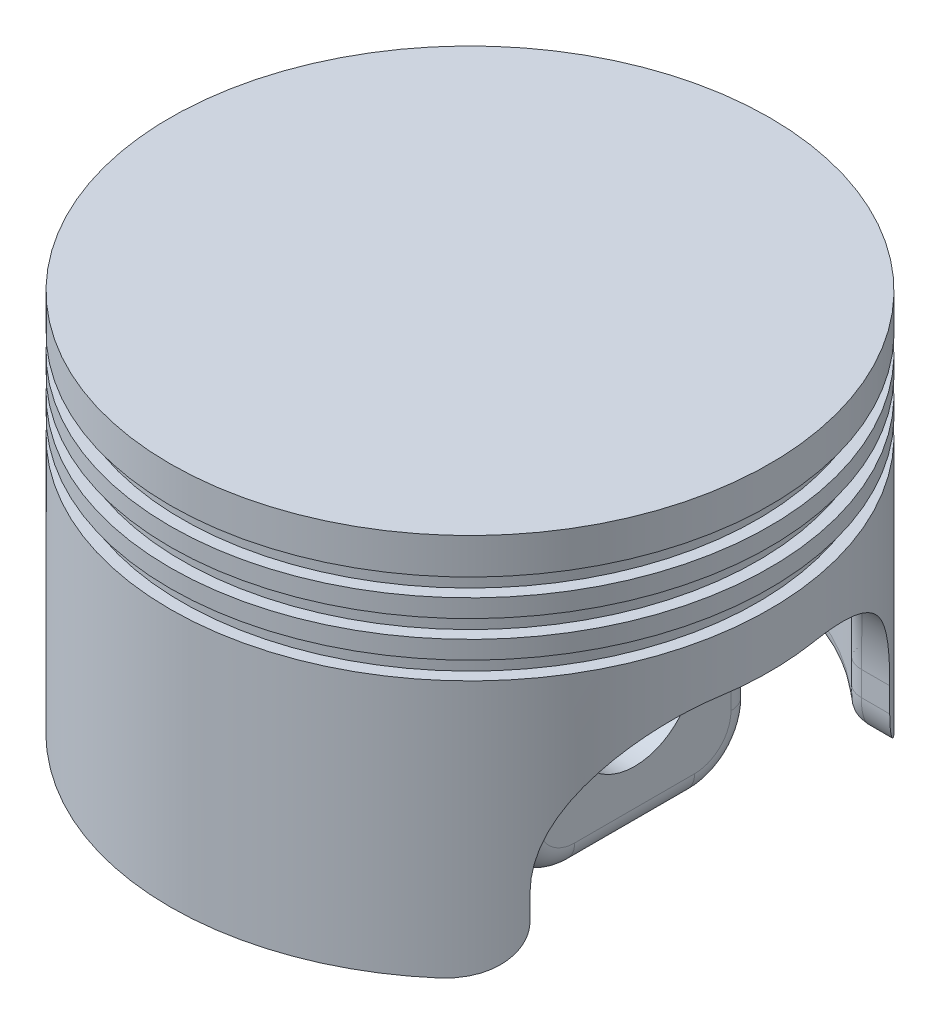
SolidWorks part; units mm, degrees
ref_plane "Alzado" through (0, 0, 0) normal (0, 0, 1) x (1, 0, 0)
ref_plane "Planta" through (0, 0, 0) normal (0, 1, 0) x (1, 0, 0)
ref_plane "Vista lateral" through (0, 0, 0) normal (1, 0, 0) x (0, 0, -1)
sketch "Croquis1" plane through (0, 0, 0) normal (1, 0, 0) x (0, 0, -1)
  line L0 (0, 0) -> (63.5, 0)
  line L1 (63.5, 0) -> (63.5, -81.28)
  line L2 (63.5, -81.28) -> (57.15, -81.28)
  line L3 (57.15, -81.28) -> (57.15, -19)
  line L4 (57.15, -19) -> (0, -19)
  line L5 (0, -19) -> (0, 0)
  dimension "D1" = 63.5
  dimension "D2" = 81.28
  dimension "D3" = 6.35
  dimension "D4" = 19
revolve "Revolución3" add sketch "Croquis1" angle 360 about L5
sketch "Croquis5" plane through (0, 0, 0) normal (0, 0, 1) x (1, 0, 0)
  line L0 (63.5, -11.43) -> (60.96, -11.43)
  line L1 (60.96, -11.43) -> (60.96, -7.62)
  line L2 (60.96, -7.62) -> (63.5, -7.62)
  line L3 (63.5, -7.62) -> (63.5, -11.43)
  line L4 (63.5, 0) -> (-63.5, 0) construction
  dimension "D1" = 7.62
  dimension "D2" = 3.81
  dimension "D3" = 2.54
  dimension "D4" = 63.5
ref_axis "Eje1" through (0, -85.344, 0) along (0, 1, 0)
revolve "Cortar-Revolución1" cut sketch "Croquis5" angle 360 about axis through (0, -85.344, 0) along (0, 1, 0)
pattern_linear "MatrizL1" count 3 spacing 7.62 along (0, -1, 0) of "Cortar-Revolución1"
sketch "Croquis7" plane through (0, 0, 0) normal (1, 0, 0) x (0, 0, -1)
  line L0 (0, -85.344) -> (0, 4.064) construction
  line L1 (-38.1, -38.1) -> (38.1, -38.1)
  line L2 (-38.1, -38.1) -> (-38.1, -81.28)
  line L3 (-38.1, -81.28) -> (38.1, -81.28)
  line L4 (38.1, -38.1) -> (38.1, -81.28)
  line L5 (-38.1, -38.1) -> (38.1, -81.28) construction
  line L6 (-38.1, -81.28) -> (38.1, -38.1) construction
  line L7 (-57.15, -81.28) -> (57.15, -81.28) construction
  line L8 (63.5, 0) -> (-63.5, 0) construction
  point P0 (0, -59.69)
  dimension "D1" = 76.2
  dimension "D2" = 38.1
extrude "Cortar-Extruir1" cut sketch "Croquis7" against normal mid plane 214
fillet "Redondeo1" radius 28 4 edges at (-46.6985, -38.1, -38.1) (-46.6985, -38.1, 38.1) (46.6985, -38.1, -38.1) (46.6985, -38.1, 38.1)
sketch "Croquis8" plane through (0, -19, 0) normal (0, -1, 0) x (1, 0, 0)
  line L1 (-34.875, -25.4) -> (-15.875, -25.4)
  line L2 (-34.875, -25.4) -> (-34.875, 25.4)
  line L3 (-34.875, 25.4) -> (-15.875, 25.4)
  line L4 (-15.875, -25.4) -> (-15.875, 25.4)
  line L5 (-34.875, -25.4) -> (-15.875, 25.4) construction
  line L6 (-34.875, 25.4) -> (-15.875, -25.4) construction
  point P0 (-25.375, 0)
  point P5 (0, 0)
  dimension "D1" = 19
  dimension "D2" = 15.875
  dimension "D3" = 50.8
extrude "Saliente-Extruir1" add sketch "Croquis8" along normal blind 63.5
mirror "Simetría1" about plane through (0, 0, 0) normal (1, 0, 0) of "Saliente-Extruir1"
sketch "Croquis9" plane through (-34.875, 0, 0) normal (-1, 0, 0) x (0, 0, 1)
  line L0 (25.4, -82.5) -> (-25.4, -82.5) construction
  circle A0 centre (0, -57.1) radius 12.7
  point P2 (0, 0)
  dimension "D1" = 25.4
  dimension "D2" = 25.4
extrude "Cortar-Extruir2" cut sketch "Croquis9" against normal blind 134.5
fillet "Redondeo2" radius 12.7 4 edges at (25.375, -82.5, -25.4) (25.375, -82.5, 25.4) (-25.375, -82.5, 25.4) (-25.375, -82.5, -25.4)
fillet "Redondeo3" radius 10 4 edges at (-46.6985, -81.28, 38.1) (-46.6985, -81.28, -38.1) (46.6985, -81.28, -38.1) (46.6985, -81.28, 38.1)
fillet "Redondeo4" radius 5 20 edges at (34.875, -44.4, 25.4) (34.875, -78.7803, 21.6803) (34.875, -44.4, -25.4) (34.875, -78.7803, -21.6803) (15.875, -44.4, -25.4) (15.875, -78.7803, -21.6803) (15.875, -44.4, 25.4) (15.875, -78.7803, 21.6803) (-34.875, -44.4, 25.4) (-34.875, -78.7803, 21.6803) (-34.875, -44.4, -25.4) (-34.875, -78.7803, -21.6803) (-15.875, -44.4, -25.4) (-15.875, -78.7803, -21.6803) (-15.875, -44.4, 25.4) (-15.875, -78.7803, 21.6803) (34.875, -82.5, 0) (15.875, -82.5, 0) (-34.875, -82.5, 0) (-15.875, -82.5, 0)
fillet "Redondeo5" radius 5 16 edges at (41.3657, -76.2692, 39.4335) (42.5971, -68.69, 38.1) (50.4318, -43.6881, 26.8841) (57.15, -38.1, 0) (46.055, -51.2516, -33.8387) (42.5971, -68.69, -38.1) (40.0022, -78.1316, -40.816) (0, -81.28, -57.15) (-41.3657, -76.2692, -39.4335) (-42.5971, -68.69, -38.1) (-50.4318, -43.6881, -26.8841) (-57.15, -38.1, 0) (-46.055, -51.2516, 33.8387) (-42.5971, -68.69, 38.1) (-40.0022, -78.1316, 40.816) (0, -81.28, 57.15)
fillet "Redondeo6" radius 5 1 edges at (0, -19, -57.15)
